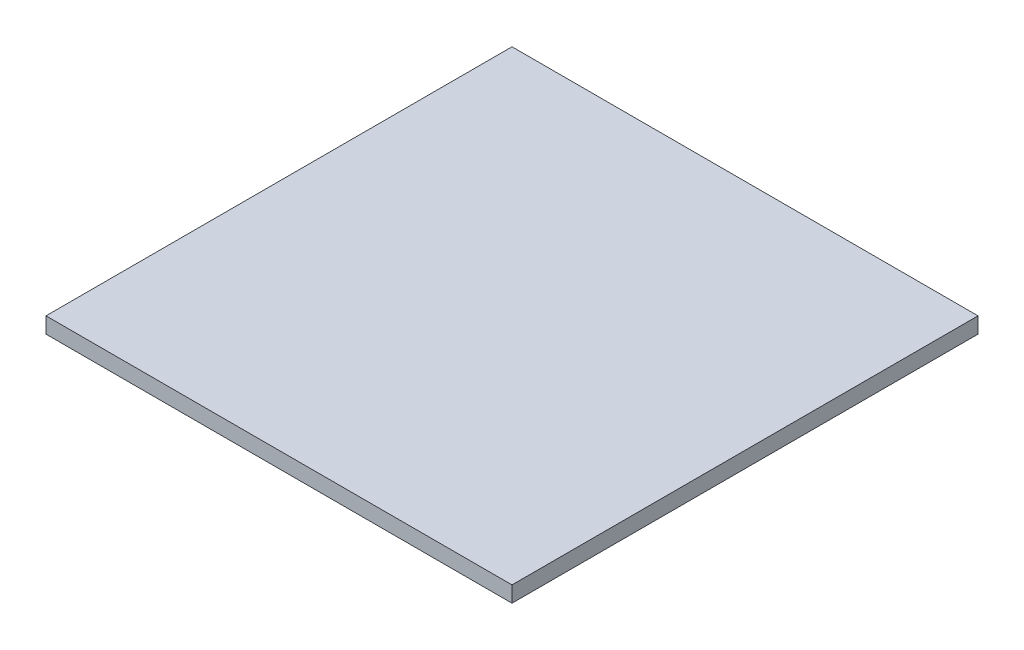
SolidWorks part; units mm, degrees
ref_plane "Front Plane" through (0, 0, 0) normal (0, 0, 1) x (1, 0, 0)
ref_plane "Top Plane" through (0, 0, 0) normal (0, 1, 0) x (1, 0, 0)
ref_plane "Right Plane" through (0, 0, 0) normal (1, 0, 0) x (0, 0, -1)
sketch "Sketch1" plane through (0, 0, 0) normal (0, 1, 0) x (1, 0, 0)
  line L0 (-539.4098, 0) -> (19.3902, 0)
  line L1 (19.3902, 0) -> (19.3902, 558.8)
  line L2 (19.3902, 558.8) -> (-539.4098, 558.8)
  line L3 (-539.4098, 558.8) -> (-539.4098, 0)
extrude "Boss-Extrude1" add sketch "Sketch1" along normal blind 19.05
